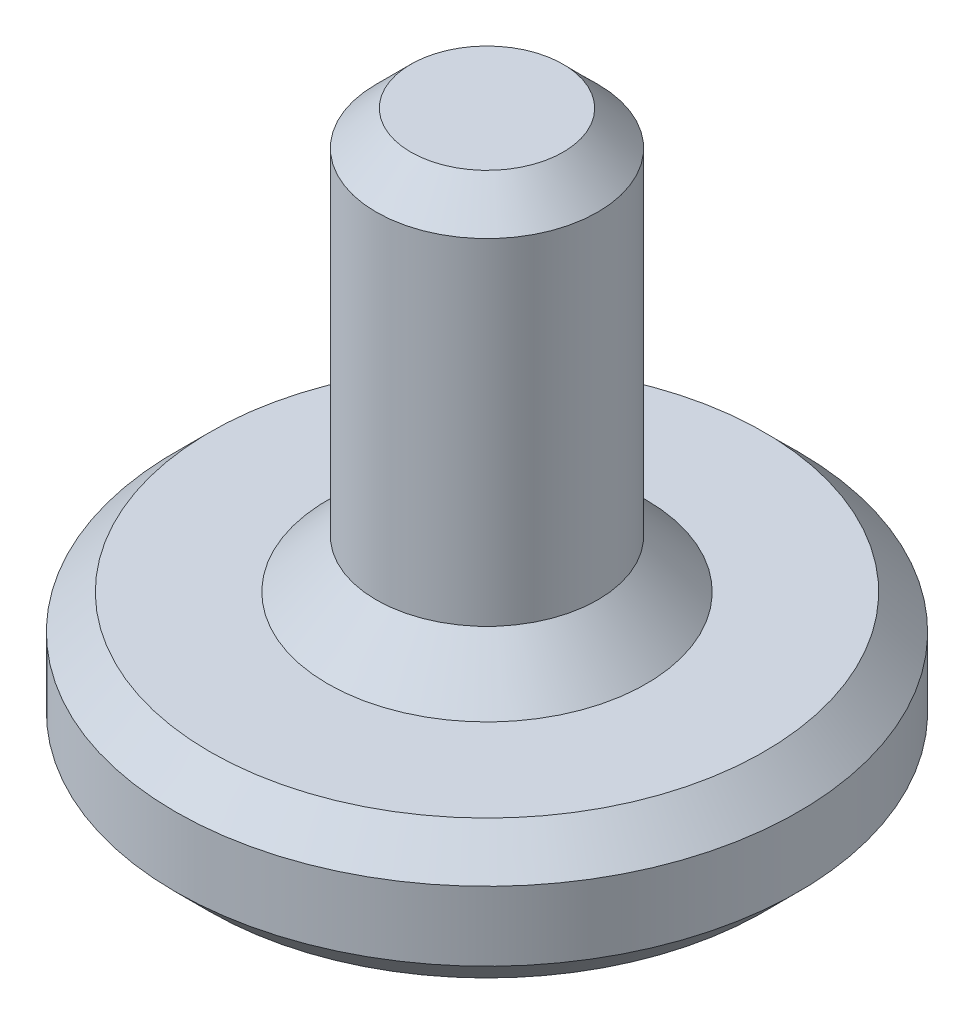
SolidWorks part; units mm, degrees
ref_plane "Front Plane" through (0, 0, 0) normal (0, 0, 1) x (1, 0, 0)
ref_plane "Top Plane" through (0, 0, 0) normal (0, 1, 0) x (1, 0, 0)
ref_plane "Right Plane" through (0, 0, 0) normal (1, 0, 0) x (0, 0, -1)
sketch "Sketch1" plane through (0, 0, 0) normal (0, 1, 0) x (1, 0, 0)
  circle A0 centre (0, 0) radius 4.5
  circle A1 centre (0, 0) radius 1.6
  dimension "D1" = 3.2
  dimension "D2" = 9
extrude "Boss-Extrude1" add sketch "Sketch1" along normal blind 2
extrude "Boss-Extrude2" add sketch "Sketch1<2>" along normal blind 8.05 contours A1 region at (0, 0, 0)
sketch "Sketch1<2>" plane through (0, 0, 0) normal (0, 1, 0) x (1, 0, 0) same geometry as "Sketch1"
chamfer "Chamfer1" distance 0.7 1 edges at (0, 2, 1.6)
chamfer "Chamfer2" distance 0.5 angle 45 2 edges at (0, 2, 4.5) (0, 0, 4.5)
chamfer "Chamfer3" distance 0.5 angle 45 1 edges at (0, 8.05, 1.6)
equation "\"D2@Sketch2\"=1.5-0.04"
